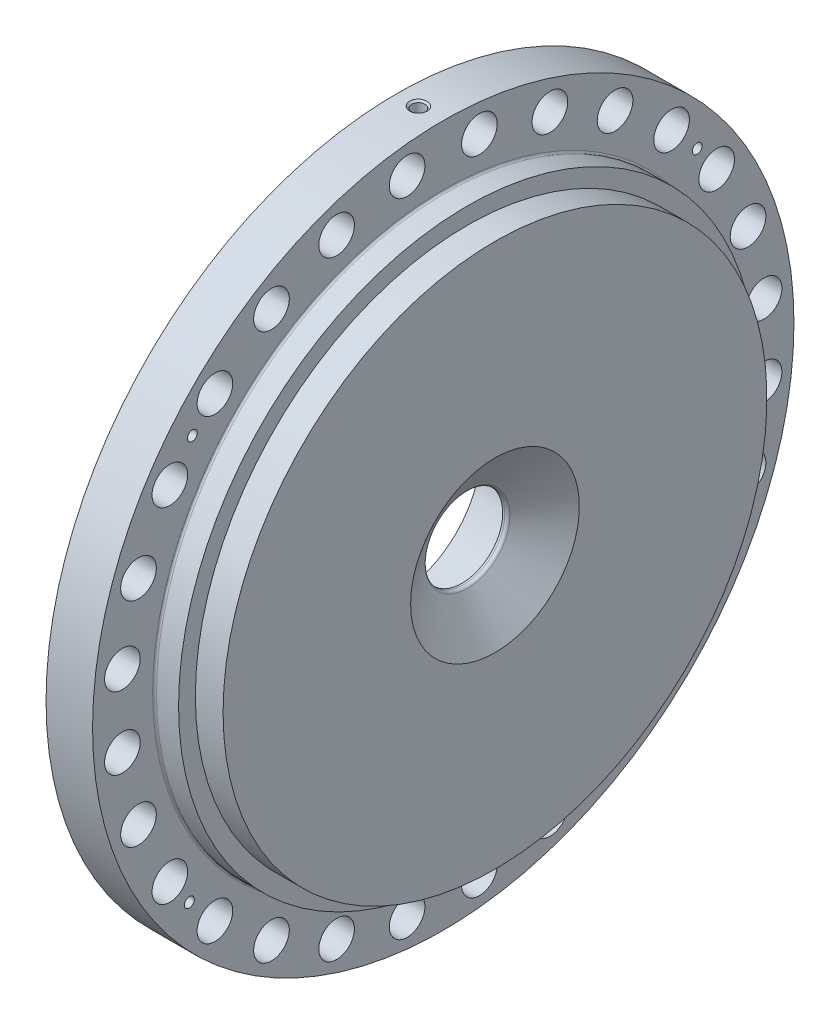
SolidWorks part; units mm, degrees
other "Markup1"
sketch "Sketch22" plane through (-5.9944, 281.051, 281.051) normal (-0.6486, 0.3883, 0.6546) x (0.7525, 0.1979, 0.6281)
material "CD4Mc-U Duplex Stainless Steel"
ref_plane "Front Plane" through (0, 0, 0) normal (0, 0, 1) x (1, 0, 0)
ref_plane "Top Plane" through (0, 0, 0) normal (0, 1, 0) x (1, 0, 0)
ref_plane "Right Plane" through (0, 0, 0) normal (1, 0, 0) x (0, 0, -1)
sketch "Sketch1" plane through (0, 0, 0) normal (0, 0, 1) x (1, 0, 0)
  line L13 (-4.7752, 67.5132) -> (-4.7752, 180.9496)
  line L14 (-4.7752, 281.051) -> (32.512, 281.051)
  line L15 (32.512, 281.051) -> (32.512, 231.3686)
  line L16 (32.512, 231.3686) -> (51.7398, 231.3686)
  line L17 (51.7398, 231.3686) -> (51.7398, 217.9066)
  line L18 (51.7398, 217.9066) -> (73.9648, 217.9066)
  line L19 (73.9648, 217.9066) -> (73.9648, 67.6275)
  line L22 (0, 0) -> (159.4613, 0) construction
  line L27 (-4.7752, 228.9937) -> (0, 228.9937)
  line L28 (0, 228.9937) -> (0, 180.9496)
  line L29 (0, 180.9496) -> (-4.7752, 180.9496)
  line L30 (-4.7752, 228.9937) -> (-4.7752, 281.051)
  line L32 (-4.7752, 67.5132) -> (47.625, 67.5132)
  line L35 (47.625, 67.5132) -> (47.625, 32.5628)
  line L36 (47.625, 32.5628) -> (49.2384, 32.5628)
  line L37 (51.8928, 33.9958) -> (73.9648, 67.6275)
  arc A0 (49.2384, 32.5628) -> (51.8928, 33.9958) centre (49.2384, 35.7378) ccw
  point P18 (50.9524, 32.5628)
  dimension "D10" = 3.175
  dimension "D1" = 78.74
  dimension "D2" = 41.4528
  dimension "D3" = 19.2278
  dimension "D4" = 3.3274
  dimension "D5" = 281.051
  dimension "D6" = 228.9937
  dimension "D7" = 231.3686
  dimension "D8" = 217.9066
  dimension "D9" = 180.9496
  dimension "D11" = 4.7752
  dimension "D12" = 32.5628
  dimension "D13" = 52.4002
  dimension "D14" = 67.5132
  dimension "D16" = 67.6275
revolve "Revolve1" add sketch "Sketch1" angle 360 about L22
sketch "Sketch4" plane through (-4.7752, 0, 0) normal (-1, 0, 0) x (0, 0, 1)
  line L0 (0, 0) -> (0, 281.051) construction
  line L1 (0, 0) -> (28.9721, 257.1355) construction
  circle A1 centre (28.9721, 257.1355) radius 14.2875
  circle A2 centre (0, 0) radius 258.7625 construction
  dimension "D2" = 28.575
  dimension "D3" = 517.525
  dimension "D1" = 6.429
extrude "Cut-Extrude1" cut sketch "Sketch4" against normal through all
pattern_circular "CirPattern2" count 28 over 360 about axis through (-4.7752, 0, 0) along (-1, 0, 0) of "Cut-Extrude1"
sketch "Sketch5" plane through (0, 0, 0) normal (-1, 0, 0) x (0, 0, 1)
  line L0 (0, 0) -> (53.4138, 199.3429) construction
  line L2 (0, 0) -> (0, 281.051) construction
  circle A0 centre (0, 0) radius 206.375 construction
  circle A1 centre (53.4138, 199.3429) radius 9.525
  circle A3 centre (0, 0) radius 281.051 construction
  dimension "D1" = 412.75
  dimension "D3" = 19.05
  dimension "D2" = 15
hole_wizard "3/4-10 Tapped Hole1" positions "Sketch7" profile "Sketch8" tap size "3/4-10" standard "ANSI Inch"
sketch "Sketch7" plane through (0, 0, 0) normal (-1, 0, 0) x (0, 0, 1)
  point P0 (53.4138, 199.3429)
sketch "Sketch8" plane through (0, 199.3429, 53.4138) normal (0, 1, 0) x (0, 0, 1)
  line L0 (0, 0) -> (0, 30.4074)
  line L1 (0, 30.4074) -> (8.3337, 25.4)
  line L2 (8.3337, 25.4) -> (8.3337, 1.8263)
  line L3 (8.3337, 1.8263) -> (10.16, 0)
  line L5 (10.16, 0) -> (0, 0)
  line L6 (-8.3337, 1.8263) -> (-10.16, 0) construction
  line L10 (0, 30.4074) -> (-8.3337, 25.4) construction
  line L11 (0, -6.35) -> (0, 107.95) construction
  dimension "Tap Drill Dia." = 16.6675
  dimension "Tap Drill Depth" = 25.4
  dimension "Near C'Sink Dia." = 20.32
  dimension "Near C'Sink Angle" = 90
  dimension "Drill Angle" = 118
cosmetic thread "Hole Thread2" parameters "D1"=12.7, "D2"=19.05
pattern_circular "CirPattern3" count 12 over 360 about axis through (47.625, 0, 0) along (-1, 0, 0) of "3/4-10 Tapped Hole1"
cosmetic thread "Hole Thread3" parameters "D1"=12.7, "D2"=19.05
cosmetic thread "Hole Thread4" parameters "D1"=12.7, "D2"=19.05
cosmetic thread "Hole Thread5" parameters "D1"=12.7, "D2"=19.05
cosmetic thread "Hole Thread6" parameters "D1"=12.7, "D2"=19.05
cosmetic thread "Hole Thread7" parameters "D1"=12.7, "D2"=19.05
cosmetic thread "Hole Thread8" parameters "D1"=12.7, "D2"=19.05
cosmetic thread "Hole Thread9" parameters "D1"=12.7, "D2"=19.05
cosmetic thread "Hole Thread10" parameters "D1"=12.7, "D2"=19.05
cosmetic thread "Hole Thread11" parameters "D1"=12.7, "D2"=19.05
cosmetic thread "Hole Thread12" parameters "D1"=12.7, "D2"=19.05
cosmetic thread "Hole Thread13" parameters "D1"=12.7, "D2"=19.05
sketch "Sketch9" plane through (-4.7752, 0, 0) normal (-1, 0, 0) x (0, 0, 1)
  line L0 (0, 0) -> (0, 94.996) construction
  line L1 (0, 0) -> (67.1723, 67.1723) construction
  circle A0 centre (0, 0) radius 94.996 construction
  circle A1 centre (67.1723, 67.1723) radius 11.1125
  dimension "D1" = 189.992
  dimension "D3" = 22.225
  dimension "D2" = 45
hole_wizard "7/8-9 Tapped Hole1" positions "3DSketch1" profile "Sketch10" tap size "7/8-9" standard "ANSI Inch"
sketch3d "3DSketch1"
  point P0 (-4.7752, 67.1723, 67.1723)
sketch "Sketch10" plane through (-4.7752, 67.1723, 67.1723) normal (0, 1, 0) x (0, 0, 1)
  line L0 (0, 0) -> (0, 31.2422)
  line L1 (0, 31.2422) -> (9.7231, 25.4)
  line L2 (9.7231, 25.4) -> (9.7231, 2.0244)
  line L3 (9.7231, 2.0244) -> (11.7475, 0)
  line L5 (11.7475, 0) -> (0, 0)
  line L6 (-9.7231, 2.0244) -> (-11.7475, 0) construction
  line L10 (0, 31.2422) -> (-9.7231, 25.4) construction
  line L11 (0, -6.35) -> (0, 107.95) construction
  dimension "Tap Drill Dia." = 19.4462
  dimension "Tap Drill Depth" = 25.4
  dimension "Near C'Sink Dia." = 23.495
  dimension "Near C'Sink Angle" = 90
  dimension "Drill Angle" = 118
cosmetic thread "Hole Thread14" parameters "D1"=44.45, "D2"=22.225
pattern_circular "CirPattern4" count 4 over 360 about axis through (47.625, 0, 0) along (-1, 0, 0) of "7/8-9 Tapped Hole1"
cosmetic thread "Hole Thread15" parameters "D1"=44.45, "D2"=22.225
cosmetic thread "Hole Thread16" parameters "D1"=44.45, "D2"=22.225
cosmetic thread "Hole Thread17" parameters "D1"=44.45, "D2"=22.225
sketch "Sketch11" plane through (-4.7752, 0, 0) normal (-1, 0, 0) x (0, 0, 1)
  line L0 (0, 0) -> (201.0962, 162.8445) construction
  line L1 (0, 0) -> (258.7625, 0) construction
  circle A0 centre (0, 0) radius 258.7625 construction
  circle A2 centre (201.0962, 162.8445) radius 4.7625
  dimension "D1" = 517.525
  dimension "D3" = 9.525
  dimension "D2" = 39
hole_wizard "Tap Drill for 3/8-16 Tap1" positions "3DSketch9" profile "Sketch21" hole size "3/8-16" standard "ANSI Inch"
sketch3d "3DSketch9"
  point P0 (-4.7752, 162.8445, 201.0962)
sketch "Sketch21" plane through (-4.7752, 162.8445, 201.0962) normal (0, 1, 0) x (0, 0, 1)
  line L0 (0, 0) -> (0, 43.0247)
  line L1 (0, 43.0247) -> (3.9687, 40.64)
  line L2 (3.9687, 40.64) -> (3.9687, 0.635)
  line L3 (3.9687, 0.635) -> (4.6037, 0)
  line L5 (4.6037, 0) -> (0, 0)
  line L6 (-3.9687, 0.635) -> (-4.6037, 0) construction
  line L10 (0, 43.0247) -> (-3.9688, 40.64) construction
  line L11 (0, -6.35) -> (0, 107.95) construction
  dimension "Hole Dia." = 7.9375
  dimension "Hole Depth" = 40.64
  dimension "Near C'Sink Dia." = 9.2075
  dimension "Near C'Sink Angle" = 90
  dimension "Drill Angle" = 118
ref_plane "Plane2" through (0, 281.051, 0) normal (0, 1, 0) x (1, 0, 0)
sketch "Sketch20" plane through (0, 281.051, 0) normal (0, 1, 0) x (1, 0, 0)
  line L0 (-4.7752, 0) -> (12.5984, 0) construction
  line L1 (-4.7752, 281.051) -> (-4.7752, -281.051) construction
  dimension "D1" = 17.3736
pattern_circular "CirPattern5" count 56 over 360 about axis through (0, 0, 0) along (-1, 0, 0) skipping 1, 2, 3, 4, 5, 6, 7, 8, 9, 10, 11, 12, 13, 14, 15, 17, 18, 19, 20, 21, 22, 23, 24, 25, 26, 27, 29, 30, 31, 32, 33, 34, 35, 36, 37, 38, 39, 40, 41, 42, 43, 45, 46, 47, 48, 49, 50, 51, 52, 53, 54, 55 of "Tap Drill for 3/8-16 Tap1"
hole_wizard "1/2-13 Tapped Hole4" positions "3DSketch8" profile "Sketch19" tap size "1/2-13" standard "ANSI Inch"
sketch3d "3DSketch8"
  point P0 (12.5984, 281.051, 0)
sketch "Sketch19" plane through (12.5984, 281.051, 0) normal (1, 0, 0) x (0, 0, 1)
  line L0 (0, 0) -> (0, 38.2715)
  line L1 (0, 38.2715) -> (5.3581, 35.052)
  line L2 (5.3581, 35.052) -> (5.3581, 1.3651)
  line L3 (5.3581, 1.3651) -> (6.985, 0)
  line L5 (6.985, 0) -> (0, 0)
  line L6 (-5.3581, 1.3651) -> (-6.985, 0) construction
  line L10 (0, 38.2715) -> (-5.3581, 35.052) construction
  line L11 (0, -6.35) -> (0, 107.95) construction
  dimension "Tap Drill Dia." = 10.7163
  dimension "Tap Drill Depth" = 35.052
  dimension "Near C'Sink Dia." = 13.97
  dimension "Near C'Sink Angle" = 100
  dimension "Drill Angle" = 118
cosmetic thread "Hole Thread24" parameters "D1"=25.4, "D2"=12.7
fillet "Fillet1" radius 1.524 1 edges at (32.512, 0, 231.3686)
fillet "Fillet2" radius 4.7752 1 edges at (0, 0, 228.9937)
fillet "Fillet3" radius 1.524 1 edges at (0, 0, 180.9496)
